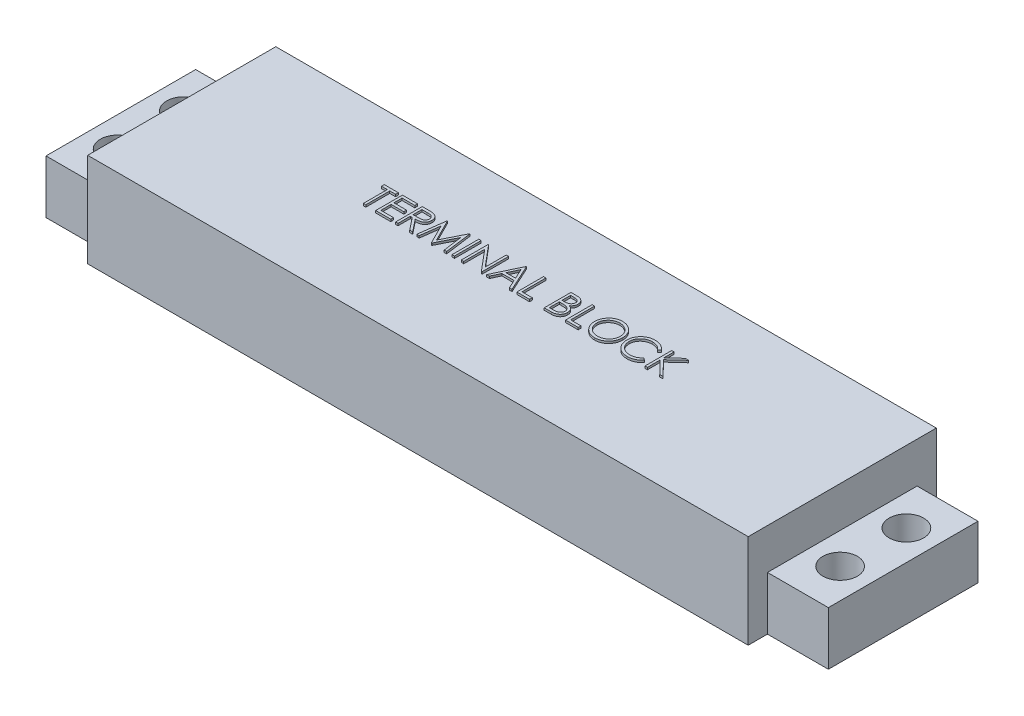
SolidWorks part; units mm, degrees
ref_plane "Front Plane" through (0, 0, 0) normal (0, 0, 1) x (1, 0, 0)
ref_plane "Top Plane" through (0, 0, 0) normal (0, 1, 0) x (1, 0, 0)
ref_plane "Right Plane" through (0, 0, 0) normal (1, 0, 0) x (0, 0, -1)
sketch "Sketch1" plane through (0, 0, 0) normal (0, 1, 0) x (1, 0, 0)
  line L0 (-39.243, 8.89) -> (-46.482, 8.89)
  line L1 (-39.243, -11.176) -> (39.243, -11.176)
  line L2 (-39.243, -11.176) -> (-39.243, 11.176)
  line L3 (-39.243, 11.176) -> (39.243, 11.176)
  line L4 (39.243, -11.176) -> (39.243, 11.176)
  line L5 (-39.243, -11.176) -> (39.243, 11.176) construction
  line L6 (-39.243, 11.176) -> (39.243, -11.176) construction
  line L7 (-46.482, 8.89) -> (-46.482, -8.89)
  line L8 (-46.482, -8.89) -> (-39.243, -8.89)
  line L9 (-6.3012, 0) -> (6.3012, 0) construction
  line L10 (0, 6.3012) -> (0, -6.3012) construction
  line L11 (46.482, -8.89) -> (39.243, -8.89)
  line L12 (46.482, 8.89) -> (46.482, -8.89)
  line L13 (39.243, 8.89) -> (46.482, 8.89)
  point P0 (0, 0)
  point P14 (0, 0)
  point P16 (0, 0)
  point P21 (-46.482, 0)
  dimension "D1" = 78.486
  dimension "D2" = 22.352
  dimension "D3" = 92.964
  dimension "D4" = 17.78
extrude "Boss-Extrude1" add sketch "Sketch1" along normal blind 11.176 contours L3 L4 L1 L2
extrude "Boss-Extrude2" add sketch "Sketch1<4>" along normal blind 6.35 contours L7 L8 L2 L0 | L13 L4 L11 L12 region at (-42.8625, 0, 0) region at (42.8625, 0, 0)
sketch "Sketch1<4>" plane through (0, 0, 0) normal (0, 1, 0) x (1, 0, 0) same geometry as "Sketch1"
sketch "Sketch2" plane through (0, 6.35, 0) normal (0, 1, 0) x (1, 0, 0)
  line L0 (0, 13.4551) -> (0, -16.0408) construction
  line L1 (-46.482, 8.89) -> (-46.482, -8.89) construction
  line L2 (-49.8215, 0) -> (6.086, 0) construction
  circle A0 centre (-42.926, 3.937) radius 2.05
  circle A1 centre (-42.926, -3.937) radius 2.05
  circle A2 centre (42.926, -3.937) radius 2.05
  circle A3 centre (42.926, 3.937) radius 2.05
  point P11 (0, 0)
  dimension "D1" = 4.1
  dimension "D2" = 3.556
  dimension "D3" = 7.874
extrude "Cut-Extrude1" cut sketch "Sketch2" against normal through all
sketch "Sketch3" plane through (0, 11.176, 0) normal (0, 1, 0) x (1, 0, 0)
  line L0 (-27.422, 0) -> (27.0256, 0) construction
  text T0 "TERMINAL BLOCK"
extrude "Boss-Extrude3" add sketch "Sketch3" along normal blind 0.254
